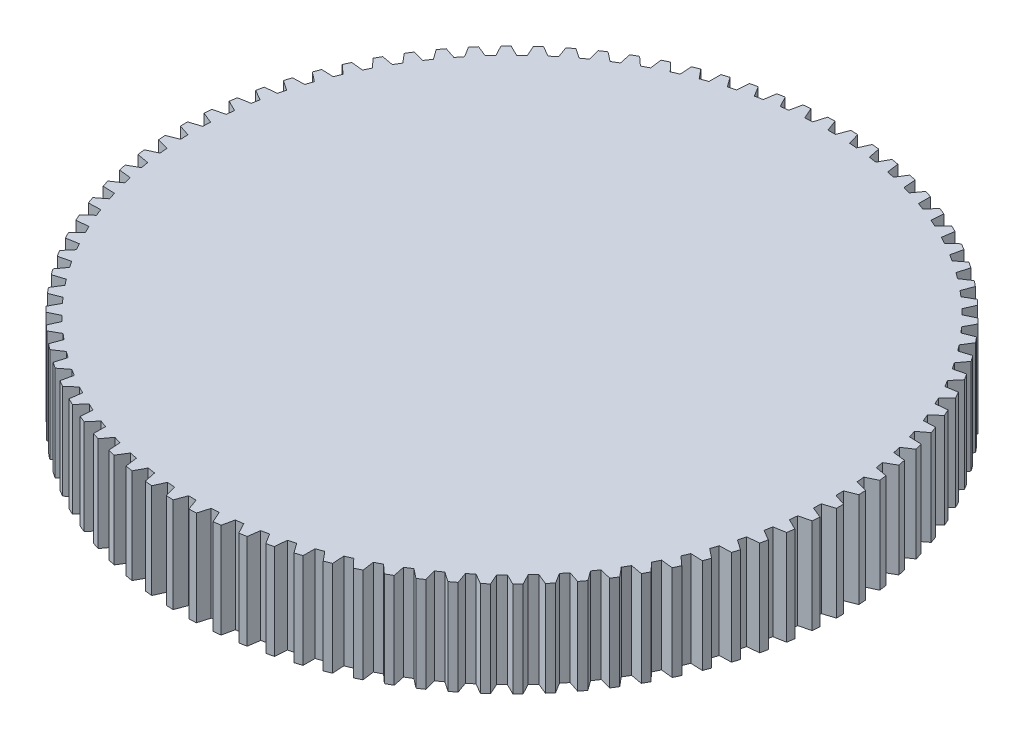
SolidWorks part; units mm, degrees
ref_plane "Front Plane" through (0, 0, 0) normal (0, 0, 1) x (1, 0, 0)
ref_plane "Top Plane" through (0, 0, 0) normal (0, 1, 0) x (1, 0, 0)
ref_plane "Right Plane" through (0, 0, 0) normal (1, 0, 0) x (0, 0, -1)
sketch "Sketch1" plane through (0, 0, 0) normal (0, 1, 0) x (1, 0, 0)
  line L0 (0, 0) -> (-28.8706, -16.4906) construction
  line L1 (-25.6111, -13.8265) -> (-24.5689, -13.6477)
  line L2 (-24.92, -15.0364) -> (-24.2366, -14.2295)
  line L3 (0, 0) -> (-37.4245, -18.039) construction
  line L4 (-26.5132, -12.0063) -> (-25.4611, -11.9006)
  line L5 (-25.9082, -13.2614) -> (-25.1702, -12.5042)
  line L6 (-27.2861, -10.1276) -> (-26.2292, -10.0956)
  line L7 (-26.7702, -11.4218) -> (-25.9811, -10.7179)
  line L8 (-27.9261, -8.1995) -> (-26.8695, -8.2413)
  line L9 (-27.5017, -9.5266) -> (-26.6654, -8.8795)
  line L10 (-28.4301, -6.2315) -> (-27.379, -6.3469)
  line L11 (-28.0993, -7.585) -> (-27.2199, -6.9978)
  line L12 (-28.7955, -4.2332) -> (-27.755, -4.4216)
  line L13 (-28.5599, -5.6064) -> (-27.6417, -5.082)
  line L14 (-29.0207, -2.2142) -> (-27.9958, -2.4747)
  line L15 (-28.8814, -3.6005) -> (-27.9289, -3.1414)
  line L16 (-29.1044, -0.1844) -> (-28.1003, -0.5158)
  line L17 (-29.0622, -1.5771) -> (-28.08, -1.1855)
  line L18 (-29.0464, 1.8463) -> (-28.0678, 1.4456)
  line L19 (-29.1015, 0.454) -> (-28.0943, 0.7761)
  line L20 (-28.8468, 3.8679) -> (-27.8986, 3.4)
  line L21 (-28.9989, 2.4829) -> (-27.9717, 2.734)
  line L22 (-28.5068, 5.8708) -> (-27.5935, 5.3378)
  line L23 (-28.7551, 4.4998) -> (-27.7129, 4.6786)
  line L24 (-28.0278, 7.845) -> (-27.1539, 7.2496)
  line L25 (-28.3711, 6.4946) -> (-27.319, 6.6003)
  line L26 (-27.4123, 9.781) -> (-26.582, 9.1261)
  line L27 (-27.849, 8.4579) -> (-26.792, 8.4899)
  line L28 (-26.6632, 11.6694) -> (-25.8807, 10.9582)
  line L29 (-27.1911, 10.3799) -> (-26.1345, 10.3381)
  line L30 (-25.7842, 13.5009) -> (-25.0532, 12.7368)
  line L31 (-26.4008, 12.2514) -> (-25.3497, 12.136)
  line L32 (-24.7797, 15.2666) -> (-24.1037, 14.4534)
  line L33 (-25.4819, 14.0632) -> (-24.4414, 13.8748)
  line L34 (-23.6544, 16.958) -> (-23.0368, 16.0996)
  line L35 (-24.4388, 15.8065) -> (-23.414, 15.5459)
  line L36 (-22.4138, 18.5667) -> (-21.8576, 17.6674)
  line L37 (-23.2767, 17.4727) -> (-22.2725, 17.1413)
  line L38 (-21.0641, 20.085) -> (-20.572, 19.149)
  line L39 (-22.0012, 19.0539) -> (-21.0226, 18.6532)
  line L40 (-19.6117, 21.5054) -> (-19.1861, 20.5374)
  line L41 (-20.6184, 20.5422) -> (-19.6702, 20.0742)
  line L42 (-18.0638, 22.8211) -> (-17.7067, 21.8257)
  line L43 (-19.1353, 21.9304) -> (-18.222, 21.3975)
  line L44 (-16.4279, 24.0255) -> (-16.1411, 23.0077)
  line L45 (-17.5589, 23.2118) -> (-16.685, 22.6164)
  line L46 (-14.7119, 25.113) -> (-14.4968, 24.0776)
  line L47 (-15.8969, 24.3801) -> (-15.0667, 23.7252)
  line L48 (-12.9243, 26.078) -> (-12.782, 25.0302)
  line L49 (-14.1575, 25.4296) -> (-13.375, 24.7184)
  line L50 (-11.0737, 26.9161) -> (-11.0048, 25.8609)
  line L51 (-12.3492, 26.3553) -> (-11.6181, 25.5912)
  line L52 (-9.1691, 27.623) -> (-9.174, 26.5655)
  line L53 (-10.4806, 27.1525) -> (-9.8047, 26.3393)
  line L54 (-7.2199, 28.1953) -> (-7.2986, 27.1408)
  line L55 (-8.561, 27.8174) -> (-7.9435, 26.9591)
  line L56 (-5.2355, 28.6302) -> (-5.3875, 27.5838)
  line L57 (-6.5997, 28.3469) -> (-6.0435, 27.4475)
  line L58 (-3.2256, 28.9257) -> (-3.4503, 27.8924)
  line L59 (-4.6063, 28.7382) -> (-4.1142, 27.8022)
  line L60 (-1.2, 29.0803) -> (-1.4962, 28.0651)
  line L61 (-2.5904, 28.9895) -> (-2.1648, 28.0215)
  line L62 (0.8314, 29.0931) -> (0.4652, 28.1012)
  line L63 (-0.5619, 29.0996) -> (-0.2048, 28.1043)
  line L64 (2.8588, 28.9643) -> (2.4243, 28.0002)
  line L65 (1.4694, 29.0679) -> (1.7561, 28.0501)
  line L66 (4.8723, 28.6943) -> (4.3716, 27.7629)
  line L67 (3.4935, 28.8946) -> (3.7085, 27.8592)
  line L68 (6.8621, 28.2845) -> (6.2976, 27.3904)
  line L69 (5.5006, 28.5805) -> (5.6429, 27.5327)
  line L70 (8.8184, 27.7369) -> (8.1929, 26.8843)
  line L71 (7.4808, 28.1272) -> (7.5497, 27.072)
  line L72 (10.7317, 27.0542) -> (10.0483, 26.2473)
  line L73 (9.4247, 27.5368) -> (9.4198, 26.4794)
  line L74 (12.5928, 26.2397) -> (11.8547, 25.4825)
  line L75 (11.3226, 26.8123) -> (11.2439, 25.7578)
  line L76 (14.3925, 25.2974) -> (13.6034, 24.5935)
  line L77 (13.1653, 25.9572) -> (13.0133, 24.9107)
  line L78 (16.1221, 24.2318) -> (15.2858, 23.5846)
  line L79 (14.9439, 24.9756) -> (14.7193, 23.9423)
  line L80 (17.7732, 23.0481) -> (16.8938, 22.4609)
  line L81 (16.6497, 23.8723) -> (16.3536, 22.8572)
  line L82 (19.3376, 21.7522) -> (18.4194, 21.2277)
  line L83 (18.2744, 22.6527) -> (17.9082, 21.6608)
  line L84 (20.8079, 20.3503) -> (19.8553, 19.8911)
  line L85 (19.8101, 21.3228) -> (19.3755, 20.3588)
  line L86 (22.1767, 18.8492) -> (21.1945, 18.4576)
  line L87 (21.2492, 19.889) -> (20.7485, 18.9576)
  line L88 (23.4376, 17.2563) -> (22.4304, 16.9342)
  line L89 (22.5849, 18.3582) -> (22.0204, 17.4641)
  line L90 (24.5842, 15.5794) -> (23.557, 15.3283)
  line L91 (23.8104, 16.7381) -> (23.185, 15.8855)
  line L92 (25.6111, 13.8265) -> (24.5689, 13.6477)
  line L93 (24.92, 15.0364) -> (24.2366, 14.2295)
  line L94 (26.5132, 12.0063) -> (25.4611, 11.9006)
  line L95 (25.9082, 13.2614) -> (25.1702, 12.5042)
  line L96 (27.2861, 10.1276) -> (26.2292, 10.0956)
  line L97 (26.7702, 11.4218) -> (25.9811, 10.7179)
  line L98 (27.9261, 8.1995) -> (26.8695, 8.2413)
  line L99 (27.5017, 9.5266) -> (26.6654, 8.8795)
  line L100 (28.4301, 6.2315) -> (27.379, 6.3469)
  line L101 (28.0993, 7.585) -> (27.2199, 6.9978)
  line L102 (28.7955, 4.2332) -> (27.755, 4.4216)
  line L103 (28.5599, 5.6064) -> (27.6417, 5.082)
  line L104 (29.0207, 2.2142) -> (27.9958, 2.4747)
  line L105 (28.8814, 3.6005) -> (27.9289, 3.1414)
  line L106 (29.1044, 0.1844) -> (28.1003, 0.5158)
  line L107 (29.0622, 1.5771) -> (28.08, 1.1855)
  line L108 (29.0464, -1.8463) -> (28.0678, -1.4456)
  line L109 (29.1015, -0.454) -> (28.0943, -0.7761)
  line L110 (28.8468, -3.8679) -> (27.8986, -3.4)
  line L111 (28.9989, -2.4829) -> (27.9717, -2.734)
  line L112 (28.5068, -5.8708) -> (27.5935, -5.3378)
  line L113 (28.7551, -4.4998) -> (27.7129, -4.6786)
  line L114 (28.0278, -7.845) -> (27.1539, -7.2496)
  line L115 (28.3711, -6.4946) -> (27.319, -6.6003)
  line L116 (27.4123, -9.781) -> (26.582, -9.1261)
  line L117 (27.849, -8.4579) -> (26.792, -8.4899)
  line L118 (26.6632, -11.6694) -> (25.8807, -10.9582)
  line L119 (27.1911, -10.3799) -> (26.1345, -10.3381)
  line L120 (25.7842, -13.5009) -> (25.0532, -12.7368)
  line L121 (26.4008, -12.2514) -> (25.3497, -12.136)
  line L122 (24.7797, -15.2666) -> (24.1037, -14.4534)
  line L123 (25.4819, -14.0632) -> (24.4414, -13.8748)
  line L124 (23.6544, -16.958) -> (23.0368, -16.0996)
  line L125 (24.4388, -15.8065) -> (23.414, -15.5459)
  line L126 (22.4138, -18.5667) -> (21.8576, -17.6674)
  line L127 (23.2767, -17.4727) -> (22.2725, -17.1413)
  line L128 (21.0641, -20.085) -> (20.572, -19.149)
  line L129 (22.0012, -19.0539) -> (21.0226, -18.6532)
  line L130 (19.6117, -21.5054) -> (19.1861, -20.5374)
  line L131 (20.6184, -20.5422) -> (19.6702, -20.0742)
  line L132 (18.0638, -22.8211) -> (17.7067, -21.8257)
  line L133 (19.1353, -21.9304) -> (18.222, -21.3975)
  line L134 (16.4279, -24.0255) -> (16.1411, -23.0077)
  line L135 (17.5589, -23.2118) -> (16.685, -22.6164)
  line L136 (14.7119, -25.113) -> (14.4968, -24.0776)
  line L137 (15.8969, -24.3801) -> (15.0667, -23.7252)
  line L138 (12.9243, -26.078) -> (12.782, -25.0302)
  line L139 (14.1575, -25.4296) -> (13.375, -24.7184)
  line L140 (11.0737, -26.9161) -> (11.0048, -25.8609)
  line L141 (12.3492, -26.3553) -> (11.6181, -25.5912)
  line L142 (9.1691, -27.623) -> (9.174, -26.5655)
  line L143 (10.4806, -27.1525) -> (9.8047, -26.3393)
  line L144 (7.2199, -28.1953) -> (7.2986, -27.1408)
  line L145 (8.561, -27.8174) -> (7.9435, -26.9591)
  line L146 (5.2355, -28.6302) -> (5.3875, -27.5838)
  line L147 (6.5997, -28.3469) -> (6.0435, -27.4475)
  line L148 (3.2256, -28.9257) -> (3.4503, -27.8924)
  line L149 (4.6063, -28.7382) -> (4.1142, -27.8022)
  line L150 (1.2, -29.0803) -> (1.4962, -28.0651)
  line L151 (2.5904, -28.9895) -> (2.1648, -28.0215)
  line L152 (-0.8314, -29.0931) -> (-0.4652, -28.1012)
  line L153 (0.5619, -29.0996) -> (0.2048, -28.1043)
  line L154 (-2.8588, -28.9643) -> (-2.4243, -28.0002)
  line L155 (-1.4694, -29.0679) -> (-1.7561, -28.0501)
  line L156 (-4.8723, -28.6943) -> (-4.3716, -27.7629)
  line L157 (-3.4935, -28.8946) -> (-3.7085, -27.8592)
  line L158 (-6.8621, -28.2845) -> (-6.2976, -27.3904)
  line L159 (-5.5006, -28.5805) -> (-5.6429, -27.5327)
  line L160 (-8.8184, -27.7369) -> (-8.1929, -26.8843)
  line L161 (-7.4808, -28.1272) -> (-7.5497, -27.072)
  line L162 (-10.7317, -27.0542) -> (-10.0483, -26.2473)
  line L163 (-9.4247, -27.5368) -> (-9.4198, -26.4794)
  line L164 (-12.5928, -26.2397) -> (-11.8547, -25.4825)
  line L165 (-11.3226, -26.8123) -> (-11.2439, -25.7578)
  line L166 (-14.3925, -25.2974) -> (-13.6034, -24.5935)
  line L167 (-13.1653, -25.9572) -> (-13.0133, -24.9107)
  line L168 (-16.1221, -24.2318) -> (-15.2858, -23.5846)
  line L169 (-14.9439, -24.9756) -> (-14.7193, -23.9423)
  line L170 (-17.7732, -23.0481) -> (-16.8938, -22.4609)
  line L171 (-16.6497, -23.8723) -> (-16.3536, -22.8572)
  line L172 (-19.3376, -21.7522) -> (-18.4194, -21.2277)
  line L173 (-18.2744, -22.6527) -> (-17.9082, -21.6608)
  line L174 (-20.8079, -20.3503) -> (-19.8553, -19.8911)
  line L175 (-19.8101, -21.3228) -> (-19.3755, -20.3588)
  line L176 (-22.1767, -18.8492) -> (-21.1945, -18.4576)
  line L177 (-21.2492, -19.889) -> (-20.7485, -18.9576)
  line L178 (-23.4376, -17.2563) -> (-22.4304, -16.9342)
  line L179 (-22.5849, -18.3582) -> (-22.0204, -17.4641)
  line L180 (-24.5842, -15.5794) -> (-23.557, -15.3283)
  line L181 (-23.8104, -16.7381) -> (-23.185, -15.8855)
  line L182 (-23.185, -15.8855) -> (0, 0)
  line L183 (0, 0) -> (-22.0204, -17.4641)
  circle A0 centre (0, 0) radius 29.105 construction
  circle A1 centre (0, 0) radius 28.105 construction
  arc A2 (-23.8104, -16.7381) -> (-23.4376, -17.2563) centre (0, 0) ccw
  arc A3 (-22.0204, -17.4641) -> (-22.4304, -16.9342) centre (0, 0) cw
  point P5 (-25.6111, -13.8265)
  point P6 (-24.92, -15.0364)
  point P15 (-26.5132, -12.0063)
  point P16 (-25.9082, -13.2614)
  point P21 (-27.2861, -10.1276)
  point P22 (-26.7702, -11.4218)
  point P27 (-27.9261, -8.1995)
  point P28 (-27.5017, -9.5266)
  point P33 (-28.4301, -6.2315)
  point P34 (-28.0993, -7.585)
  point P39 (-28.7955, -4.2332)
  point P40 (-28.5599, -5.6064)
  point P45 (-29.0207, -2.2142)
  point P46 (-28.8814, -3.6005)
  point P51 (-29.1044, -0.1844)
  point P52 (-29.0622, -1.5771)
  point P57 (-29.0464, 1.8463)
  point P58 (-29.1015, 0.454)
  point P63 (-28.8468, 3.8679)
  point P64 (-28.9989, 2.4829)
  point P69 (-28.5068, 5.8708)
  point P70 (-28.7551, 4.4998)
  point P75 (-28.0278, 7.845)
  point P76 (-28.3711, 6.4946)
  point P81 (-27.4123, 9.781)
  point P82 (-27.849, 8.4579)
  point P87 (-26.6632, 11.6694)
  point P88 (-27.1911, 10.3799)
  point P93 (-25.7842, 13.5009)
  point P94 (-26.4008, 12.2514)
  point P99 (-24.7797, 15.2666)
  point P100 (-25.4819, 14.0632)
  point P105 (-23.6544, 16.958)
  point P106 (-24.4388, 15.8065)
  point P111 (-22.4138, 18.5667)
  point P112 (-23.2767, 17.4727)
  point P117 (-21.0641, 20.085)
  point P118 (-22.0012, 19.0539)
  point P123 (-19.6117, 21.5054)
  point P124 (-20.6184, 20.5422)
  point P129 (-18.0638, 22.8211)
  point P130 (-19.1353, 21.9304)
  point P135 (-16.4279, 24.0255)
  point P136 (-17.5589, 23.2118)
  point P141 (-14.7119, 25.113)
  point P142 (-15.8969, 24.3801)
  point P147 (-12.9243, 26.078)
  point P148 (-14.1575, 25.4296)
  point P153 (-11.0737, 26.9161)
  point P154 (-12.3492, 26.3553)
  point P159 (-9.1691, 27.623)
  point P160 (-10.4806, 27.1525)
  point P165 (-7.2199, 28.1953)
  point P166 (-8.561, 27.8174)
  point P171 (-5.2355, 28.6302)
  point P172 (-6.5997, 28.3469)
  point P177 (-3.2256, 28.9257)
  point P178 (-4.6063, 28.7382)
  point P183 (-1.2, 29.0803)
  point P184 (-2.5904, 28.9895)
  point P189 (0.8314, 29.0931)
  point P190 (-0.5619, 29.0996)
  point P195 (2.8588, 28.9643)
  point P196 (1.4694, 29.0679)
  point P201 (4.8723, 28.6943)
  point P202 (3.4935, 28.8946)
  point P207 (6.8621, 28.2845)
  point P208 (5.5006, 28.5805)
  point P213 (8.8184, 27.7369)
  point P214 (7.4808, 28.1272)
  point P219 (10.7317, 27.0542)
  point P220 (9.4247, 27.5368)
  point P225 (12.5928, 26.2397)
  point P226 (11.3226, 26.8123)
  point P231 (14.3925, 25.2974)
  point P232 (13.1653, 25.9572)
  point P237 (16.1221, 24.2318)
  point P238 (14.9439, 24.9756)
  point P243 (17.7732, 23.0481)
  point P244 (16.6497, 23.8723)
  point P249 (19.3376, 21.7522)
  point P250 (18.2744, 22.6527)
  point P255 (20.8079, 20.3503)
  point P256 (19.8101, 21.3228)
  point P261 (22.1767, 18.8492)
  point P262 (21.2492, 19.889)
  point P267 (23.4376, 17.2563)
  point P268 (22.5849, 18.3582)
  point P273 (24.5842, 15.5794)
  point P274 (23.8104, 16.7381)
  point P279 (25.6111, 13.8265)
  point P280 (24.92, 15.0364)
  point P285 (26.5132, 12.0063)
  point P286 (25.9082, 13.2614)
  point P291 (27.2861, 10.1276)
  point P292 (26.7702, 11.4218)
  point P297 (27.9261, 8.1995)
  point P298 (27.5017, 9.5266)
  point P303 (28.4301, 6.2315)
  point P304 (28.0993, 7.585)
  point P309 (28.7955, 4.2332)
  point P310 (28.5599, 5.6064)
  point P315 (29.0207, 2.2142)
  point P316 (28.8814, 3.6005)
  point P321 (29.1044, 0.1844)
  point P322 (29.0622, 1.5771)
  point P327 (29.0464, -1.8463)
  point P328 (29.1015, -0.454)
  point P333 (28.8468, -3.8679)
  point P334 (28.9989, -2.4829)
  point P339 (28.5068, -5.8708)
  point P340 (28.7551, -4.4998)
  point P345 (28.0278, -7.845)
  point P346 (28.3711, -6.4946)
  point P351 (27.4123, -9.781)
  point P352 (27.849, -8.4579)
  point P357 (26.6632, -11.6694)
  point P358 (27.1911, -10.3799)
  point P363 (25.7842, -13.5009)
  point P364 (26.4008, -12.2514)
  point P369 (24.7797, -15.2666)
  point P370 (25.4819, -14.0632)
  point P375 (23.6544, -16.958)
  point P376 (24.4388, -15.8065)
  point P381 (22.4138, -18.5667)
  point P382 (23.2767, -17.4727)
  point P387 (21.0641, -20.085)
  point P388 (22.0012, -19.0539)
  point P393 (19.6117, -21.5054)
  point P394 (20.6184, -20.5422)
  point P399 (18.0638, -22.8211)
  point P400 (19.1353, -21.9304)
  point P405 (16.4279, -24.0255)
  point P406 (17.5589, -23.2118)
  point P411 (14.7119, -25.113)
  point P412 (15.8969, -24.3801)
  point P417 (12.9243, -26.078)
  point P418 (14.1575, -25.4296)
  point P423 (11.0737, -26.9161)
  point P424 (12.3492, -26.3553)
  point P429 (9.1691, -27.623)
  point P430 (10.4806, -27.1525)
  point P435 (7.2199, -28.1953)
  point P436 (8.561, -27.8174)
  point P441 (5.2355, -28.6302)
  point P442 (6.5997, -28.3469)
  point P447 (3.2256, -28.9257)
  point P448 (4.6063, -28.7382)
  point P453 (1.2, -29.0803)
  point P454 (2.5904, -28.9895)
  point P459 (-0.8314, -29.0931)
  point P460 (0.5619, -29.0996)
  point P465 (-2.8588, -28.9643)
  point P466 (-1.4694, -29.0679)
  point P471 (-4.8723, -28.6943)
  point P472 (-3.4935, -28.8946)
  point P477 (-6.8621, -28.2845)
  point P478 (-5.5006, -28.5805)
  point P483 (-8.8184, -27.7369)
  point P484 (-7.4808, -28.1272)
  point P489 (-10.7317, -27.0542)
  point P490 (-9.4247, -27.5368)
  point P495 (-12.5928, -26.2397)
  point P496 (-11.3226, -26.8123)
  point P501 (-14.3925, -25.2974)
  point P502 (-13.1653, -25.9572)
  point P507 (-16.1221, -24.2318)
  point P508 (-14.9439, -24.9756)
  point P513 (-17.7732, -23.0481)
  point P514 (-16.6497, -23.8723)
  point P519 (-19.3376, -21.7522)
  point P520 (-18.2744, -22.6527)
  point P525 (-20.8079, -20.3503)
  point P526 (-19.8101, -21.3228)
  point P531 (-22.1767, -18.8492)
  point P532 (-21.2492, -19.889)
  point P537 (-23.4376, -17.2563)
  point P538 (-22.5849, -18.3582)
  point P543 (-24.5842, -15.5794)
  point P544 (-23.8104, -16.7381)
  point P549 (0, 0)
  dimension "D1" = 58.21
  dimension "D2" = 1
  dimension "D3" = 40
  dimension "D4" = 4
  dimension "D5" = 0.67
  dimension "D6" = 90
extrude "Boss-Extrude1" add sketch "Sketch1" along normal blind 8.4 contours A3 L183 L182 L181 A2 L178 region at (-15.3484, 0, 11.3088)
pattern_circular "CirPattern1" count 90 over 360 about axis through (0, 8.4, 0) along (0, -1, 0) of "Boss-Extrude1" reverse direction yes
